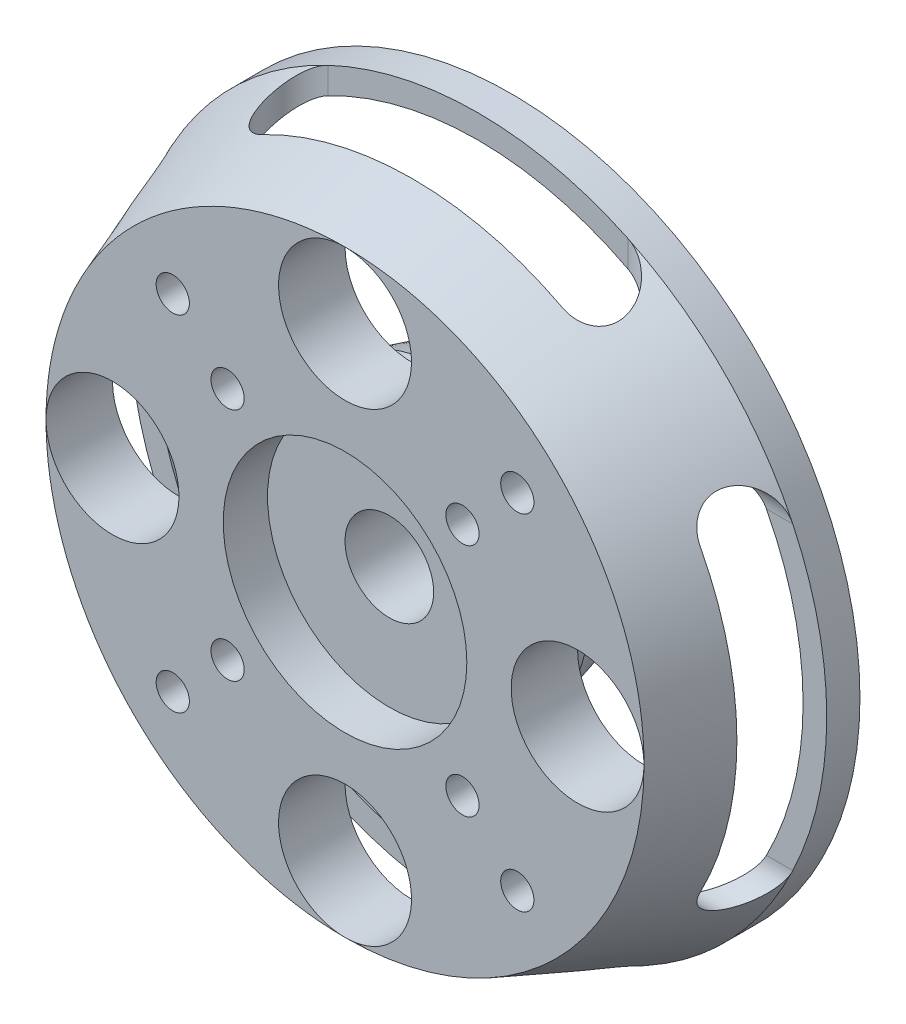
SolidWorks part; units mm, degrees
ref_plane "Front Plane" through (0, 0, 0) normal (0, 0, 1) x (1, 0, 0)
ref_plane "Top Plane" through (0, 0, 0) normal (0, 1, 0) x (1, 0, 0)
ref_plane "Right Plane" through (0, 0, 0) normal (1, 0, 0) x (0, 0, -1)
ref_axis "Z" through (0, 0, -15.75) along (0, 0, 1)
sketch "Sketch1" plane through (0, 0, 0) normal (0, 1, 0) x (1, 0, 0)
  line L0 (29.5, 15) -> (29.5, 12.3627)
  line L1 (29.5, 12.3627) -> (27.114, 6)
  line L2 (27.114, 6) -> (13, 6)
  line L3 (13, 6) -> (13, 9)
  line L4 (11.3923, 15) -> (4, 15)
  line L5 (4, 15) -> (4, 4)
  line L6 (11, 0) -> (27, 0)
  line L7 (27, 0) -> (31.5, 12)
  line L8 (31.5, 12) -> (31.5, 15)
  line L9 (31.5, 15) -> (29.5, 15)
  line L10 (0, -76.8889) -> (0, 67.6055) construction
  line L11 (11, 0) -> (11, 4)
  line L12 (11, 4) -> (4, 4)
  line L13 (4, 4) -> (4, 0) construction
  line L14 (4, 0) -> (11, 0) construction
  line L15 (11.3923, 15) -> (13, 9)
  line L16 (13, 15) -> (11.3923, 15) construction
  line L17 (13, 9) -> (13, 15) construction
  dimension "D1" = 8
  dimension "D2" = 15
  dimension "D3" = 2
  dimension "D4" = 3
  dimension "D5" = 2
  dimension "D6" = 63
  dimension "D7" = 6
  dimension "D8" = 9
  dimension "D9" = 54
  dimension "D10" = 22
  dimension "D11" = 4
  dimension "D12" = 15
  dimension "D13" = 3
revolve "Revolve1" add sketch "Sketch1" angle 360 about L10
ref_plane "Plane4" through (-31.5, 0, 0) normal (-1, 0, 0) x (0, 0, 1)
sketch "Sketch2" plane through (-31.5, 0, 0) normal (-1, 0, 0) x (0, 0, 1)
  line L0 (-9.05, -13.55) -> (-9.05, 13.55) construction
  line L1 (-12, -13.55) -> (-12, 13.55)
  line L2 (-6.1, -13.55) -> (-6.1, 13.55)
  line L3 (-15.75, 0) -> (0.75, 0) construction
  line L4 (-12.4387, -16.5) -> (-5.6613, -16.5) construction
  line L5 (-12.4387, 16.5) -> (-5.6613, 16.5) construction
  line L7 (-15, 29.5) -> (-15, -29.5) construction
  arc A0 (-12, -13.55) -> (-6.1, -13.55) centre (-9.05, -13.55) ccw
  arc A1 (-6.1, 13.55) -> (-12, 13.55) centre (-9.05, 13.55) ccw
  point P2 (-9.05, 0)
  dimension "D2" = 33
  dimension "D1" = 5.9
  dimension "D3" = 3
extrude "Cut-Extrude1" cut sketch "Sketch2" against normal blind 10
pattern_circular "CirPattern1" count 4 over 360 about axis through (0, 0, -15.75) along (0, 0, 1) of "Cut-Extrude1"
sketch "Sketch3" plane through (0, 0, 0) normal (0, 0, 1) x (1, 0, 0)
  line L0 (-21, 0) -> (0, 0) construction
  line L1 (0, 0) -> (-15.5563, 15.5563) construction
  circle A0 centre (-21, 0) radius 6
  circle A1 centre (0, 21) radius 6
  circle A2 centre (21, 0) radius 6
  circle A3 centre (0, -21) radius 6
  circle A4 centre (-15.5563, 15.5563) radius 1.5
  circle A5 centre (-10.6066, 10.6066) radius 1.5
  circle A6 centre (10.6066, 10.6066) radius 1.5
  circle A7 centre (15.5563, 15.5563) radius 1.5
  circle A8 centre (10.6066, -10.6066) radius 1.5
  circle A9 centre (15.5563, -15.5563) radius 1.5
  circle A10 centre (-10.6066, -10.6066) radius 1.5
  circle A11 centre (-15.5563, -15.5563) radius 1.5
  point P13 (0, 0)
  point P31 (0, 0)
  dimension "D1" = 12
  dimension "D5" = 3
  dimension "D2" = 21
  dimension "D4" = 45
  dimension "D6" = 7
  dimension "D7" = 15
  dimension "D3" = 4
  dimension "D8" = 4
extrude "Cut-Extrude2" cut sketch "Sketch3" against normal through all
equation "\"RotorMainLength\"= 41'rotor body longest dimension"
equation "\"OverallLength\"= 65.8'The height of the whole motor, not counting shaft protrusions"
equation "\"RotorDiameter\"= 63'Overall rotor diameter"
equation "\"RotorTopCapHeight\"= 14'Rough measurement/eyeballed. Not super critical for this; most important dim is overall length"
equation "\"RotorLargeHoleDiameter\"= 17'ID measurement with calipers"
equation "\"RotorLargeHoleTangentSpacing\"= 19'tangent to tangent on the large holes. add one diameter to achieve the center distances"
equation "\"RotorLargeHoleCenterDistance\"= \"RotorLargeHoleTangentSpacing\" + \"RotorLargeHoleDiameter\"'Center to center spacing for large hole"
equation "\"RotorSmallHoleID\"= 8'ID measurement with calipers"
equation "\"RotorSmallHoleTangentSpacing\"= 37'Tangent to Tangent (rounded to the nearest integer, real measurement was like 0.03mm off)"
equation "\"RotorSmallHoleCenterDistance\"= \"RotorSmallHoleID\" + \"RotorSmallHoleTangentSpacing\"'Center to center spacing for small holes"
equation "\"ShaftDiameter\"= 8"
equation "\"RotorShaftTopCapDiameter\"= 18'the small circular extrusion at the top of the rotor"
equation "\"RotorShaftTopCapHeight\"= 2'Height of the small cylindircal extrusion at the top of the rotor"
equation "\"RotorBoltCircleFlatDiameter\"= 30'Diameter of the flat portion where the bolt circle is drilled in the rotor"
equation "\"RotorTaperedEdgeHeight\"= 7'approximate, vertical distance of the tapered/angled edge of the rotor"
equation "\"RotorBoltCircleCenterDistance\"= 23mm'rounded, hard to measure with calipers so assuming they aren't fucking insane and chose this"
equation "\"StatorTrayHeight\"= 3+6+6\t'Rough measurement/eyeballed. Not super critical. Take up clearance in airgap; maintain overall height"
equation "\"StatorBaseOD\" = 54.00\t\t'OD of the base of the stator where the bolt circle is"
equation "\"D1@Sketch1\"=\"ShaftDiameter\""
equation "\"D2@Sketch1\"=\"StatorTrayHeight\""
equation "\"D6@Sketch1\"=\"RotorDiameter\""
equation "\"D7@Sketch3\"=15"
equation "\"D6@Sketch3\"=7"
equation "\"D1@Sketch3\"=12"
equation "\"D9@Sketch1\" = \"StatorBaseOD\""
